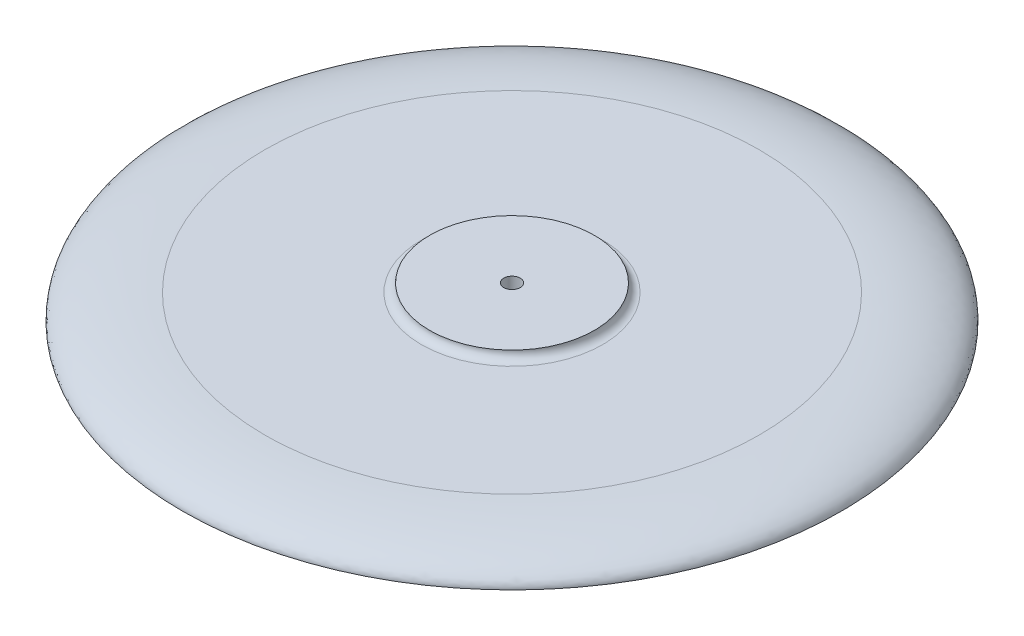
SolidWorks part; units mm, degrees
ref_plane "Front Plane" through (0, 0, 0) normal (0, 0, 1) x (1, 0, 0)
ref_plane "Top Plane" through (0, 0, 0) normal (0, 1, 0) x (1, 0, 0)
ref_plane "Right Plane" through (0, 0, 0) normal (1, 0, 0) x (0, 0, -1)
sketch "Sketch1" plane through (0, 0, 0) normal (0, 1, 0) x (1, 0, 0)
  circle A0 centre (0, 0) radius 40
  dimension "D1" = 80
extrude "Boss-Extrude1" add sketch "Sketch1" along normal blind 3
sketch "Sketch2" plane through (0, 3, 0) normal (0, 1, 0) x (1, 0, 0)
  circle A0 centre (0, 0) radius 10
extrude "Boss-Extrude2" add sketch "Sketch2" along normal blind 1
sketch "Sketch3" plane through (0, 4, 0) normal (0, 1, 0) x (1, 0, 0)
  circle A0 centre (0, 0) radius 1
extrude "Cut-Extrude1" cut sketch "Sketch3" against normal through all
fillet "Fillet1" radius 1 1 edges at (0, 3, 10)
fillet "Fillet2" radius 3 1 edges at (0, 3, 40) second distance 10 first distance on face at (0, 3, 40)
